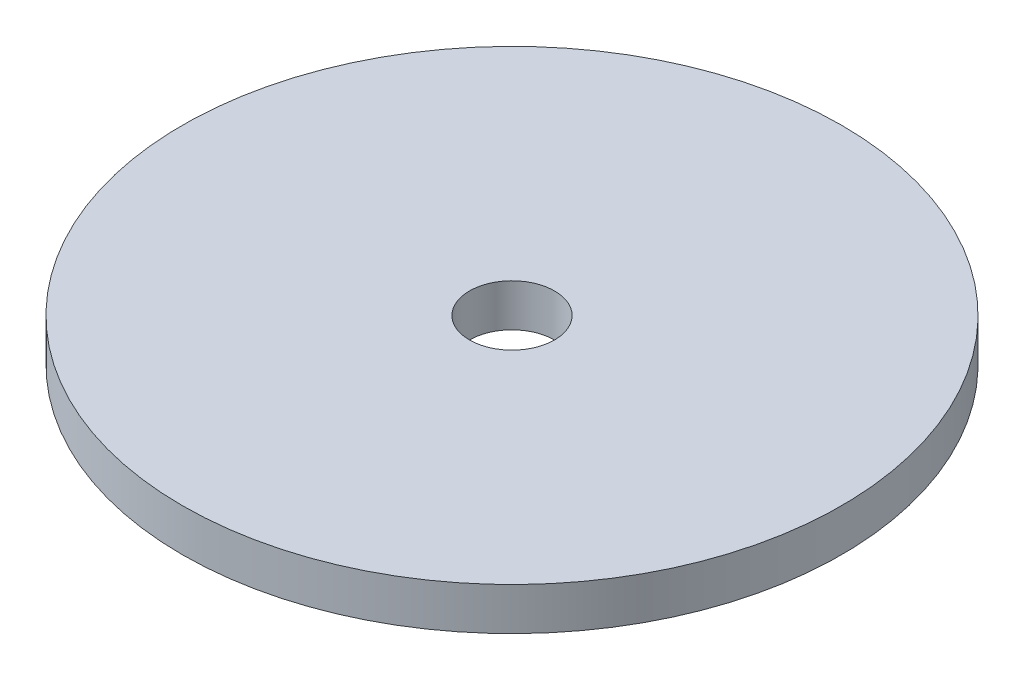
SolidWorks part; units mm, degrees
material "Gray Cast Iron"
ref_plane "Plane1" through (0, 0, 0) normal (0, 0, 1) x (1, 0, 0)
ref_plane "Plane2" through (0, 0, 0) normal (0, 1, 0) x (1, 0, 0)
ref_plane "Plane3" through (0, 0, 0) normal (1, 0, 0) x (0, 0, -1)
ref_axis "Axis1" through (-80.9, 0, 0) along (1, 0, 0)
ref_axis "Axis2" through (0, 0, -80.9) along (0, 0, 1)
ref_axis "Axis3" through (0, 50, 0) along (0, -1, 0)
sketch "Sketch1" plane through (0, 0, 0) normal (0, 1, 0) x (1, 0, 0)
  circle A0 centre (0, 0) radius 196.85
  circle A1 centre (0, 0) radius 25.4
  dimension "D1" = 393.7
  dimension "D2" = 50.8
extrude "Boss-Extrude1" add sketch "Sketch1" along normal blind 25.4
